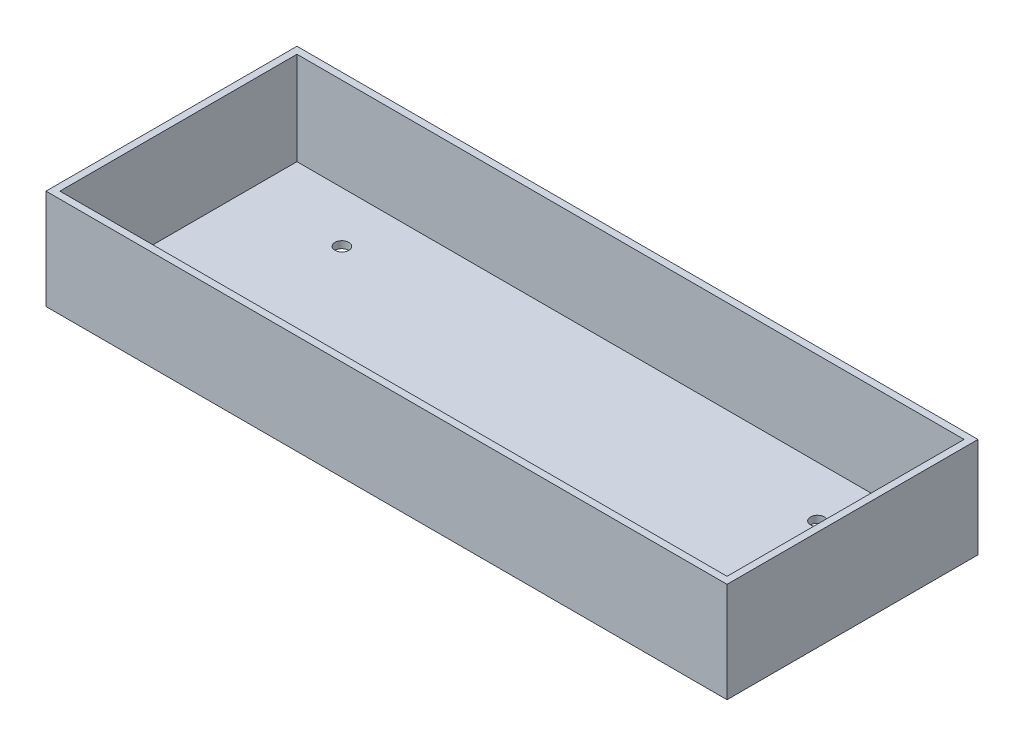
SolidWorks part; units mm, degrees
ref_plane "Plan de face" through (0, 0, 0) normal (0, 0, 1) x (1, 0, 0)
ref_plane "Plan de dessus" through (0, 0, 0) normal (0, 1, 0) x (1, 0, 0)
ref_plane "Plan de droite" through (0, 0, 0) normal (1, 0, 0) x (0, 0, -1)
sketch "Esquisse1" plane through (0, 0, 0) normal (0, 1, 0) x (1, 0, 0)
  line L0 (98.1, 72.3) -> (98.1, 0) construction
  line L1 (0, 0) -> (196.2, 0)
  line L2 (0, 0) -> (0, 72.3)
  line L3 (0, 72.3) -> (196.2, 72.3)
  line L4 (196.2, 0) -> (196.2, 72.3)
  line L5 (2, 2) -> (194.2, 2)
  line L6 (2, 2) -> (2, 70.3)
  line L7 (2, 70.3) -> (194.2, 70.3)
  line L8 (194.2, 2) -> (194.2, 70.3)
  line L9 (29.6, 72.3) -> (29.6, 0) construction
  line L10 (0, 36.15) -> (196.2, 36.15) construction
  circle A0 centre (29.6, 55.65) radius 2
  circle A1 centre (29.6, 16.65) radius 2
  circle A2 centre (166.6, 55.65) radius 2
  circle A3 centre (166.6, 16.65) radius 2
  dimension "D4" = 4
  dimension "D1" = 196.2
  dimension "D2" = 72.3
  dimension "D3" = 19.5
  dimension "D5" = 68.5
  dimension "D6" = 2
  dimension "D7" = 2
  dimension "D8" = 2
  dimension "D9" = 2
extrude "Boss.-Extru.1" add sketch "Esquisse1" along normal blind 28.8 contours L2 L3 L4 L1 | L6 L7 L8 L5
extrude "Boss.-Extru.2" add sketch "Esquisse1<3>" along normal blind 2 contours L6 L7 L8 L5 | A0 | A1 | A3 | A2
sketch "Esquisse1<3>" plane through (0, 0, 0) normal (0, 1, 0) x (1, 0, 0) same geometry as "Esquisse1"
